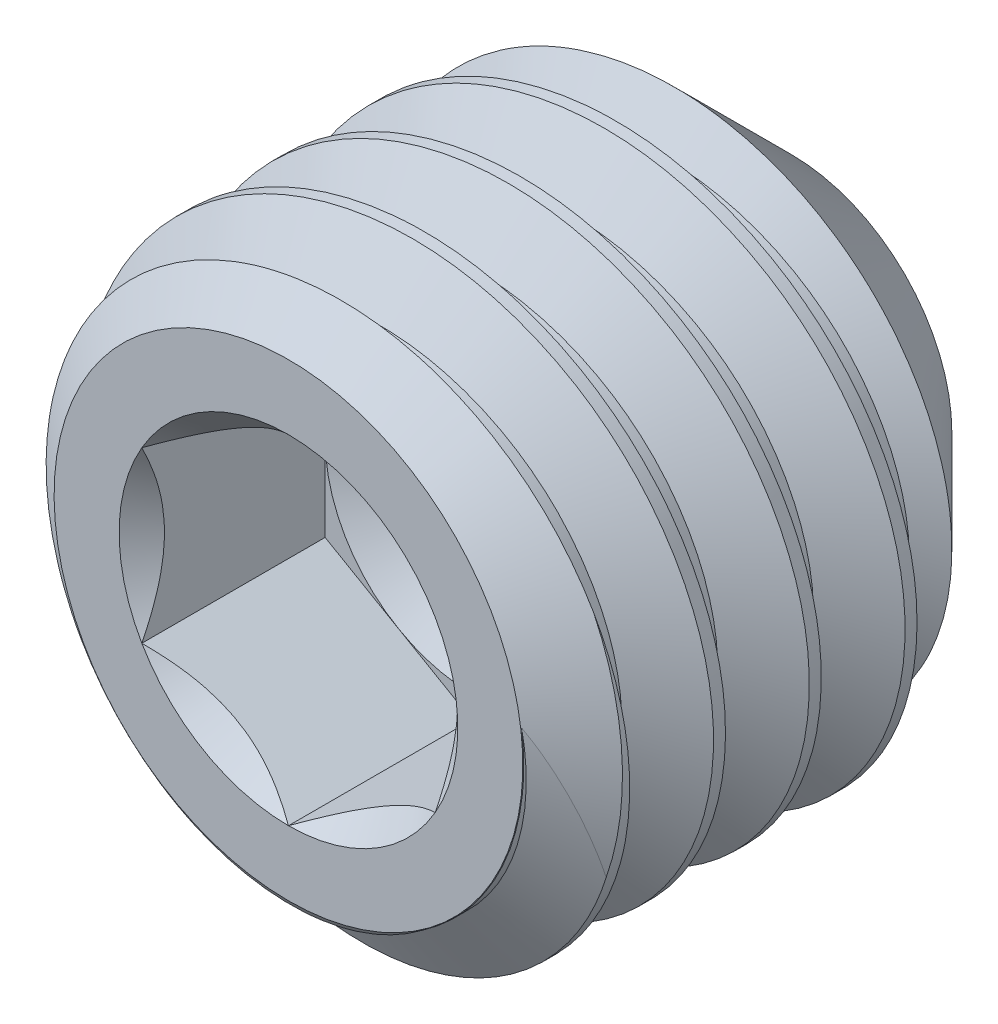
SolidWorks part; units mm, degrees
ref_plane "Front" through (0, 0, 0) normal (0, 0, 1) x (1, 0, 0)
ref_plane "Top" through (0, 0, 0) normal (0, 1, 0) x (1, 0, 0)
ref_plane "Right" through (0, 0, 0) normal (1, 0, 0) x (0, 0, -1)
sketch "Sketch22" plane through (0, 0, 0) normal (1, 0, 0) x (0, 0, -1)
  line L0 (-3.8488, 0) -> (-3.8488, 4.4399)
  line L1 (-3.8488, 4.4399) -> (-3.0716, 5.5499)
  line L2 (-3.0716, 5.5499) -> (3.1674, 5.5499)
  line L3 (3.1674, 5.5499) -> (5.6762, 3.0412)
  line L4 (5.6762, 3.0412) -> (3.8488, 0)
  line L5 (3.8488, 0) -> (-3.8488, 0)
  line L6 (3.8488, 0) -> (5.6762, 0) construction
  line L7 (5.6762, 0) -> (5.6762, 3.0412) construction
  line L8 (5.6762, -3.0412) -> (3.8488, 0) construction
  line L9 (-3.0716, -5.5499) -> (3.1674, -5.5499) construction
  dimension "Dia" = 11.0998
  dimension "Length" = 9.525
  dimension "D3" = 35
  dimension "D5" = 118
  dimension "D6" = 45
  dimension "D7" = 8.8798
revolve "Revolve1" add sketch "Sketch22" angle 360 about L6
ref_plane "Plane1" through (0, 0, -5.6762) normal (0, 0, 1) x (1, 0, 0)
sketch "Sketch27" plane through (0, 0, -5.6762) normal (0, 0, 1) x (1, 0, 0)
  circle A0 centre (0, 0) radius 5.5499 construction
  circle A1 centre (0, 0) radius 5.5499
curve "Helix/Spiral1" pitch 1.8143 height 12.6492 radius 5.5499 centre (0, 0, -5.6762) axis (0, 0, 1) start towards (1, 0, 0)
sketch "Sketch28" plane through (0, 0, 0) normal (1, 0, 0) x (0, 0, -1)
  line L0 (5.6762, 5.5499) -> (7.2637, 5.5499)
  line L1 (7.2637, 5.5499) -> (6.6287, 4.45)
  line L2 (6.6287, 4.45) -> (6.3112, 4.45)
  line L3 (6.3112, 4.45) -> (5.6762, 5.5499)
  line L4 (5.9937, 5) -> (6.9462, 5) construction
  line L6 (-3.0716, 5.5499) -> (3.1674, 5.5499) construction
  line L7 (5.6762, 14.1602) -> (5.6762, -14.1602) construction
  dimension "D1" = 0.3175
  dimension "D3" = 60
  dimension "D2" = 1.5875
sweep "Cut-Sweep2" cut profiles "Sketch28" path "Helix/Spiral1" align with end faces yes
sketch "Sketch23" plane through (0, 0, 3.8488) normal (0, 0, 1) x (1, 0, 0)
  line L1 (0, 3.2079) -> (-2.7781, 1.604)
  line L2 (-2.7781, 1.604) -> (-2.7781, -1.604)
  line L3 (-2.7781, -1.604) -> (0, -3.2079)
  line L4 (0, -3.2079) -> (2.7781, -1.604)
  line L5 (2.7781, -1.604) -> (2.7781, 1.604)
  line L6 (2.7781, 1.604) -> (0, 3.2079)
  circle A0 centre (0, 0) radius 2.7781 construction
  dimension "Hex" = 5.5562
extrude "Cut-Extrude10" cut sketch "Sketch23" against normal blind 3.4727
sketch "Sketch24" plane through (0, 0, 3.8488) normal (0, 0, 1) x (1, 0, 0)
  circle A0 centre (0, 0) radius 3.2079
extrude "Cut-Extrude11" cut sketch "Sketch24" against normal through all draft 45
sketch "Sketch26" plane through (0, 0, 0.3762) normal (0, 0, 1) x (1, 0, 0)
  circle A0 centre (0, 0) radius 2.7781 construction
  circle A1 centre (0, 0) radius 2.7781
extrude "Cut-Extrude12" cut sketch "Sketch26" against normal through all draft 60
sketch "Sketch30" plane through (0, 0, 0) normal (1, 0, 0) x (0, 0, -1)
  line L0 (-3.0716, 5.5499) -> (3.1674, 5.5499) construction
  line L1 (-3.8488, 0) -> (-3.8488, 4.4399) construction
  line L2 (5.6762, 0) -> (5.6762, 3.0412) construction
  line L3 (-3.0716, -5.5499) -> (3.1674, -5.5499) construction
  point P0 (-3.8488, 5.5499)
  point P1 (5.6762, 5.5499)
  point P2 (5.6762, -5.5499)
  point P11 (1.1404, -5.5499)
  dimension "D1" = 4.5357
sketch "Sketch31" plane through (0, 0, 0) normal (1, 0, 0) x (0, 0, -1)
  line L2 (3.8488, 0) -> (5.6762, -3.0412)
  line L3 (5.6762, 3.0412) -> (3.8488, 0)
equation "\"D7@Sketch22\"=\"Dia@Sketch22\"*.8"
equation "\"D1@Sketch28\" = \"D4@Helix/Spiral1\" * .175"
equation "\"D3@Helix/Spiral1\" = \"Length@Sketch22\" + .123"
equation "\"D1@Sketch30\" = \"D4@Helix/Spiral1\" * 2.5"
equation "\"hex Depth@Cut-Extrude10\" = \"Hex@Sketch23\" * .625"
equation "\"D2@Sketch28\" = \"D4@Helix/Spiral1\" * .875"
